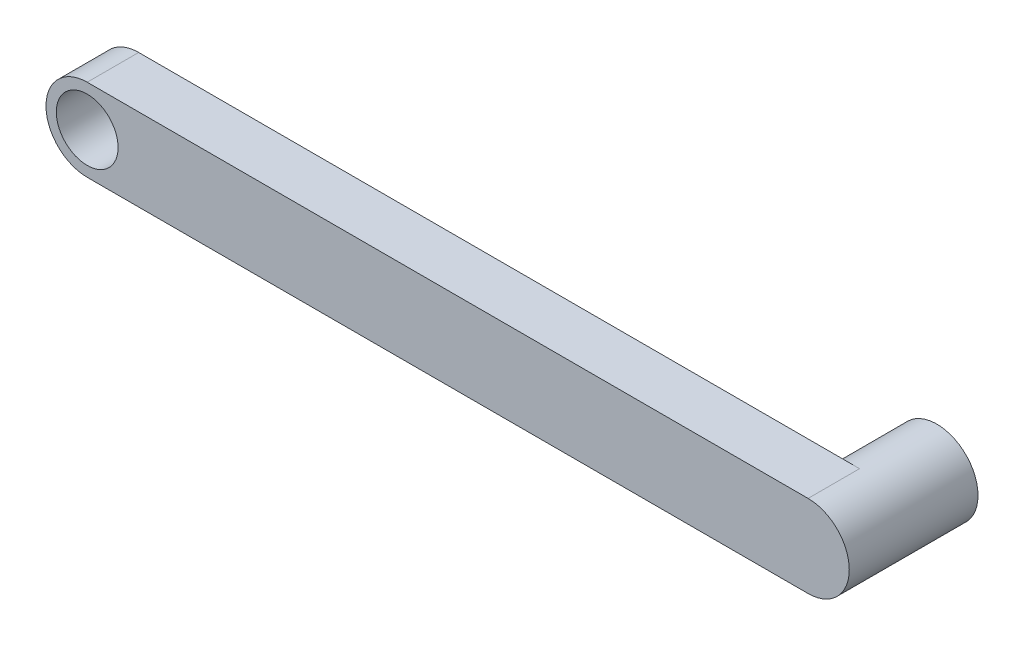
SolidWorks part; units mm, degrees
ref_plane "Front Plane" through (0, 0, 0) normal (0, 0, 1) x (1, 0, 0)
ref_plane "Top Plane" through (0, 0, 0) normal (0, 1, 0) x (1, 0, 0)
ref_plane "Right Plane" through (0, 0, 0) normal (1, 0, 0) x (0, 0, -1)
sketch "Sketch1" plane through (0, 0, 0) normal (0, 0, 1) x (1, 0, 0)
  line L4 (50, 8) -> (190, 8)
  line L7 (50, -8) -> (190, -8)
  circle A4 centre (50, 0) radius 6
  circle A6 centre (50, 0) radius 8
  circle A8 centre (190, 0) radius 8
  dimension "D1" = 140
  dimension "D7" = 12
  dimension "D8" = 2
extrude "Boss-Extrude1" add sketch "Sketch1" along normal blind 10 contours A8 L4 A6 L7 | A6 A4 | A8 region at (120, 0, 0) region at (55.4969, 5.4969, 0) region at (190, 0, 0)
extrude "Boss-Extrude2" add sketch "Sketch1<6>" against normal blind 15 contours A8 region at (190, 0, 0)
sketch "Sketch1<6>" plane through (0, 0, 0) normal (0, 0, 1) x (1, 0, 0) same geometry as "Sketch1"
